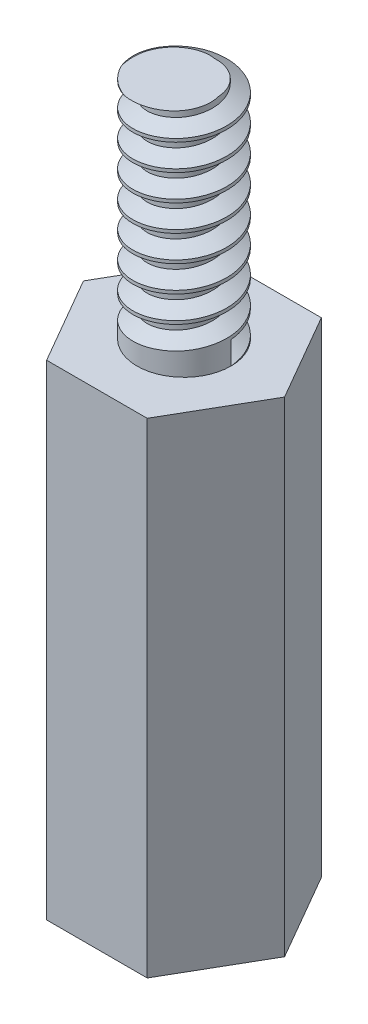
SolidWorks part; units mm, degrees
material "Brass"
ref_plane "Front Plane" through (0, 0, 0) normal (0, 0, 1) x (1, 0, 0)
ref_plane "Top Plane" through (0, 0, 0) normal (0, 1, 0) x (1, 0, 0)
ref_plane "Right Plane" through (0, 0, 0) normal (1, 0, 0) x (0, 0, -1)
sketch "Sketch1" plane through (0, 0, 0) normal (0, 1, 0) x (1, 0, 0)
  line L1 (1.3382, -2.3178) -> (2.6763, 0)
  line L2 (2.6763, 0) -> (1.3382, 2.3177)
  line L3 (1.3382, 2.3177) -> (-1.3382, 2.3178)
  line L4 (-1.3382, 2.3178) -> (-2.6763, 0)
  line L5 (-2.6763, 0) -> (-1.3382, -2.3177)
  line L6 (-1.3382, -2.3177) -> (1.3382, -2.3178)
  circle A0 centre (0, 0) radius 2.3178 construction
  point P1 (1.7811, 1.9976)
  dimension "D1" = 4.6355
extrude "Boss-Extrude1" add sketch "Sketch1" along normal blind 15
hole_wizard "CBORE for M2.5 Pan Head Machine Screw1" positions "Sketch2" profile "Sketch3" counterbore size "M2.5" standard "ANSI Metric"
sketch "Sketch2" plane through (0, 0, 0) normal (0, -1, 0) x (-1, 0, 0)
  point P0 (0, 0)
sketch "Sketch3" plane through (0, 0, 0) normal (1, 0, 0) x (0, 0, -1)
  line L0 (0, 0) -> (0, 12.8712)
  line L1 (0, 12.8712) -> (1.45, 12)
  line L2 (1.45, 12) -> (1.45, 2.1)
  line L3 (1.45, 2.1) -> (3, 2.1)
  line L4 (3, 2.1) -> (3, 0)
  line L5 (3, 0) -> (0, 0)
  line L10 (0, 12.8712) -> (-1.45, 12) construction
  line L11 (0, -6.35) -> (0, 107.95) construction
  dimension "Hole Dia." = 2.9
  dimension "Hole Depth" = 12
  dimension "C'Bore Dia." = 6
  dimension "C'Bore Depth" = 2.1
  dimension "Drill Angle" = 118
sketch "Sketch4" plane through (0, 15, 0) normal (0, 1, 0) x (1, 0, 0)
  circle A0 centre (0, 0) radius 1.25
  dimension "D1" = 2.5
extrude "Boss-Extrude2" add sketch "Sketch4" along normal blind 6
thread "Thread1" pitch 0.7 method cut profile "Thread Profile1" start angle 0, offset 0, length 10, pitch 0.7, diameter 2.5
ref_plane "Plane1" through (1.25, 15, 0) normal (0, 0, 1) x (1, 0, 0)
sketch "Thread Profile1" plane through (1.25, 15, 0) normal (0, 0, 1) x (1, 0, 0)
  line L0 (0, 0) -> (0, 0.7) construction
  line L11 (0, 0) -> (0, 0.6125)
  line L12 (0, 0.6125) -> (-0.3789, 0.3937)
  line L13 (-0.3789, 0.3937) -> (-0.3789, 0.2187)
  line L15 (-0.3789, 0.2187) -> (0, 0)
  line L17 (-0.3789, 0.3062) -> (0, 0.3062) construction
  point P2 (0, 0)
  dimension "Pitch" = 0.7
  dimension "Profile_Angle" = 60
  dimension "Profile_Land" = 0.175
  dimension "Profile_Height" = 0.3789
